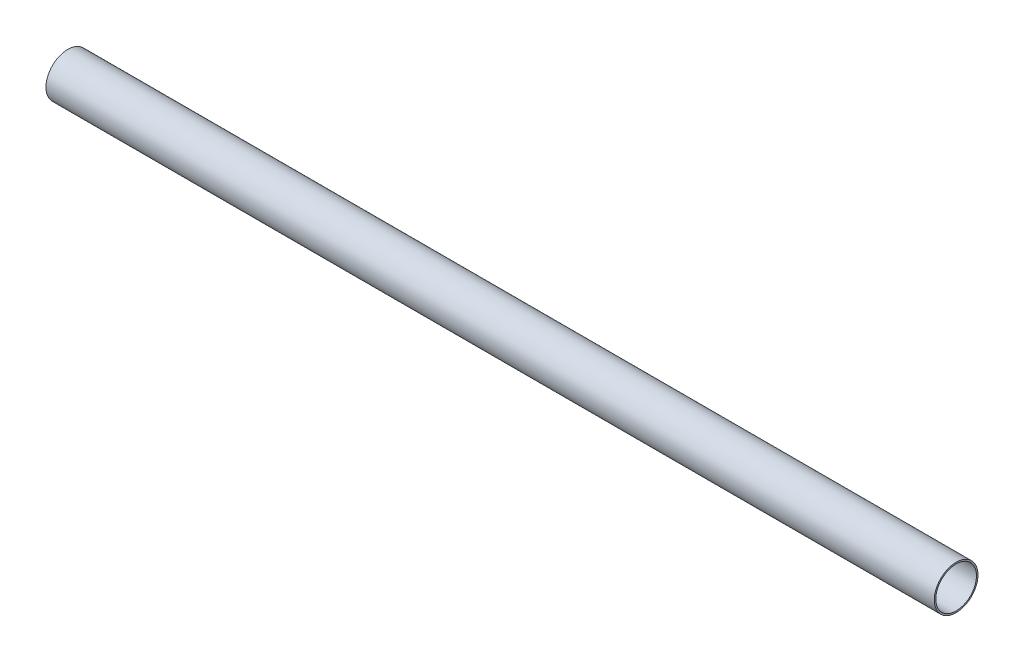
SolidWorks part; units mm, degrees
ref_plane "Front Plane" through (0, 0, 0) normal (0, 0, 1) x (1, 0, 0)
ref_plane "Top Plane" through (0, 0, 0) normal (0, 1, 0) x (1, 0, 0)
ref_plane "Right Plane" through (0, 0, 0) normal (1, 0, 0) x (0, 0, -1)
sketch "Sketch1" plane through (0, 0, 0) normal (1, 0, 0) x (0, 0, -1)
  circle A0 centre (0, 0) radius 12.7
  circle A1 centre (0, 0) radius 11.811
extrude "Boss-Extrude1" add sketch "Sketch1" along normal blind 516
